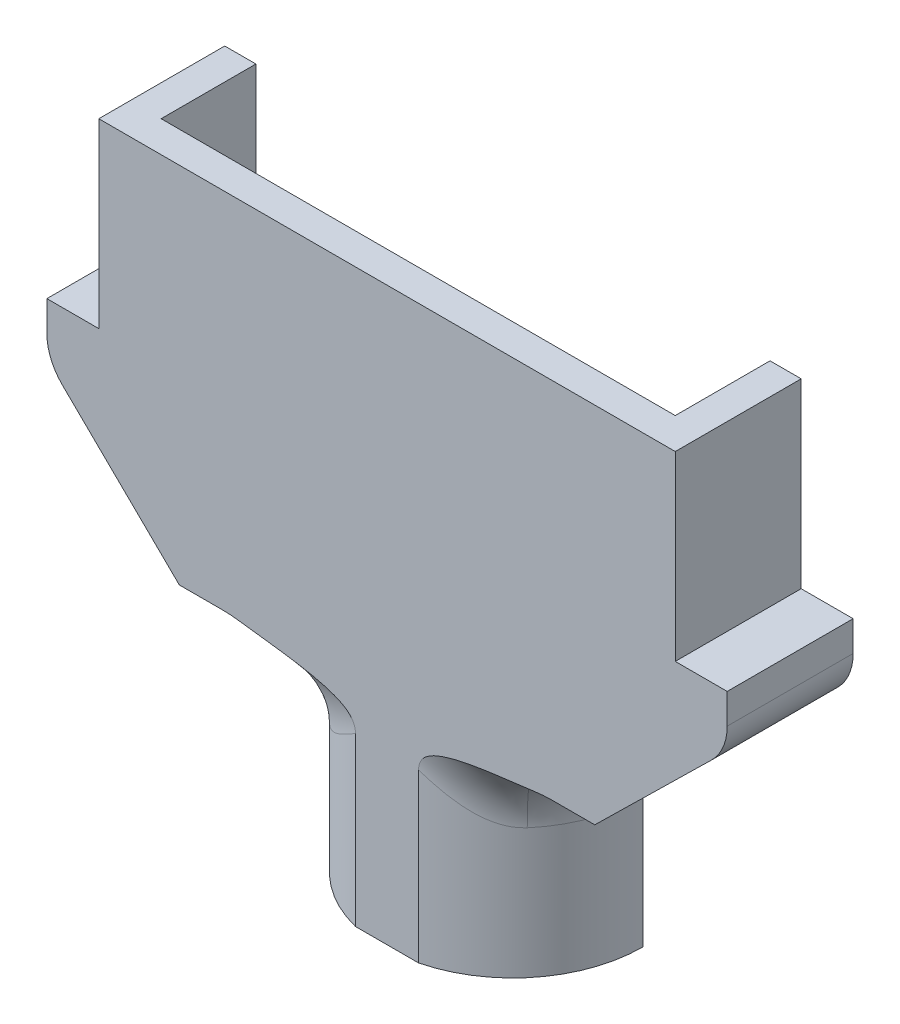
SolidWorks part; units mm, degrees
ref_plane "Alzado" through (0, 0, 0) normal (0, 0, 1) x (1, 0, 0)
ref_plane "Planta" through (0, 0, 0) normal (0, 1, 0) x (1, 0, 0)
ref_plane "Vista lateral" through (0, 0, 0) normal (1, 0, 0) x (0, 0, -1)
sketch "Croquis1" plane through (0, 0, 0) normal (0, 1, 0) x (1, 0, 0)
  line L1 (-9.4, 3.15) -> (9.4, 3.15)
  line L2 (-9.4, 3.15) -> (-9.4, -3.15)
  line L3 (-9.4, -3.15) -> (9.4, -3.15)
  line L4 (9.4, 3.15) -> (9.4, -3.15)
  line L5 (-11.4, 5.15) -> (11.4, 5.15)
  line L6 (-11.4, 5.15) -> (-11.4, -5.15)
  line L7 (-11.4, -5.15) -> (11.4, -5.15)
  line L8 (11.4, 5.15) -> (11.4, -5.15)
  point P4 (0, 3.15)
  point P6 (9.4, 0)
  point P11 (-9.4, 0)
  dimension "D1" = 18.8
  dimension "D2" = 6.3
  dimension "D3" = 2
  dimension "D4" = 2
  dimension "D5" = 2
  dimension "D6" = 2
extrude "Saliente-Extruir1" add sketch "Croquis1" along normal blind 7
sketch "Croquis3" plane through (0, 0, 0) normal (0, 0, 1) x (1, 0, 0)
  line L0 (-11.4, 0) -> (11.4, 0) construction
  line L1 (-14.4, 0) -> (14.4, 0)
  line L2 (-14.4, 0) -> (-14.4, -7)
  line L3 (-14.4, -7) -> (14.4, -7)
  line L4 (14.4, 0) -> (14.4, -7)
  line L5 (-11.4, 7) -> (-11.4, 0) construction
  line L6 (11.4, 7) -> (11.4, 0) construction
  line L8 (-5, -7) -> (5, -7)
  line L9 (-5, -7) -> (-5, -15)
  line L10 (-5, -15) -> (5, -15)
  line L11 (5, -7) -> (5, -15)
  point P14 (0, -15)
  dimension "D1" = 3
  dimension "D2" = 3
  dimension "D3" = 7
  dimension "D4" = 10
  dimension "D5" = 8
extrude "Saliente-Extruir3" add sketch "Croquis3" along normal blind 5.2 contours L4 L1 L2 L3 | L11 L3 L9 L10 region at (0, -3.5, 0) region at (0, -11, 0)
sketch "Croquis4" plane through (0, -15, 0) normal (0, -1, 0) x (1, 0, 0)
  line L1 (-9.3409, 11.3798) -> (8.5543, 11.3798)
  line L2 (-9.3409, 11.3798) -> (-9.3409, -7.874)
  line L3 (-9.3409, -7.874) -> (8.5543, -7.874)
  line L4 (8.5543, 11.3798) -> (8.5543, -7.874)
  circle A0 centre (0, 0) radius 3.4
  circle A1 centre (0, 0) radius 5
  line M5 (-5, 0) -> (5, 0)
  line M6 (5, 0) -> (5, 5.2)
  line M7 (5, 5.2) -> (-5, 5.2)
  line M8 (-5, 5.2) -> (-5, 0)
  dimension "D1" = 6.8
extrude "Cortar-Extruir1" cut sketch "Croquis4" against normal up to surface (8 mm away) contours L4 L1 L2 L3 A1 M8 M7 M6 | A0 M5 | A1 M6 M7 M8 region at (-0.3933, -15, 11.1169) region at (0, -15, 1.443) region at (0, -15, 5.1127) up to face at (9.7, -7, 2.6)
sketch "Croquis5" plane through (0, -7, 0) normal (0, -1, 0) x (1, 0, 0)
  line L1 (-3.4, 0) -> (3.4, 0)
  line L2 (-3.4, 0) -> (3.4, 0)
  arc A1 (3.4, 0) -> (-3.4, 0) centre (0, 0) ccw
  arc A2 (3.4, 0) -> (-3.4, 0) centre (0, 0) ccw
  dimension "D1" = 0
extrude "Cortar-Extruir2" cut sketch "Croquis5" against normal blind 26.4
sketch "Croquis6" plane through (0, 0, -5.15) normal (0, 0, -1) x (-1, 0, 0)
  line L4 (-11.4, 0) -> (11.4, 0)
  line L5 (11.4, 0) -> (11.4, 7)
  line L6 (11.4, 7) -> (-11.4, 7)
  line L7 (-11.4, 7) -> (-11.4, 0)
  line L8 (-11.4, 0) -> (11.4, 0)
  line L9 (11.4, 0) -> (11.4, 7)
  line L10 (11.4, 7) -> (-11.4, 7)
  line L11 (-11.4, 7) -> (-11.4, 0)
  dimension "D1" = 0
extrude "Cortar-Extruir3" cut sketch "Croquis6" against normal up to surface (5.15 mm away) up to face at (8.3, -5.5, 0)
fillet "Redondeo3" radius 3 1 edges at (0, -7, 5)
sketch "Croquis7" plane through (0, 7, 0) normal (0, 1, 0) x (1, 0, 0)
  line L0 (9.4, 0) -> (11.4, 0) construction
  line L1 (9.9, 0) -> (-9.9, 0)
  line L2 (9.9, 0) -> (9.9, -3.65)
  line L3 (9.9, -3.65) -> (-9.9, -3.65)
  line L4 (-9.9, 0) -> (-9.9, -3.65)
  line L7 (-11.4, -5.15) -> (11.4, -5.15) construction
  line L8 (11.1, 0) -> (11.1, -4.85)
  line L9 (11.1, -4.85) -> (-11.1, -4.85)
  line L10 (-11.1, -4.85) -> (-11.1, 0)
  line L11 (-11.4, 0) -> (-9.4, 0) construction
  line L12 (-11.1, 0) -> (-13.1406, 0)
  line L13 (-13.1406, 0) -> (-13.1406, -7.2853)
  line L14 (-13.1406, -7.2853) -> (14.3364, -7.2853)
  line L15 (14.3364, -7.2853) -> (14.0781, 0)
  line L16 (14.0781, 0) -> (11.1, 0)
  line L18 (11.4, -5.15) -> (11.4, 0) construction
  line L19 (-11.4, 0) -> (-11.4, -5.15) construction
  dimension "D1" = 1.2
  dimension "D2" = 1.2
  dimension "D3" = 1.5
  dimension "D4" = 1.2
  dimension "D5" = 1.5
  dimension "D6" = 1.5
extrude "Cortar-Extruir4" cut sketch "Croquis7" against normal up to surface (7 mm away) up to face at (0, 0, 2.5875)
sketch "Croquis8" plane through (0, 0, 0) normal (0, 0, -1) x (-1, 0, 0)
  line L0 (-9.9, 0) -> (-3.4, -7.5)
  line L1 (-3.4, 0) -> (-3.4, -15) construction
  line L2 (-3.4, -7.5) -> (3.4, -7.5)
  line L3 (3.4, 0) -> (3.4, -15) construction
  line L4 (3.4, -7.5) -> (9.9, 0)
  line L5 (9.9, 0) -> (-9.9, 0)
extrude "Cortar-Extruir5" cut sketch "Croquis8" against normal up to surface (3.65 mm away) up to face at (0, 3.5, 3.65)
sketch "Croquis9" plane through (0, 0, 5.2) normal (0, 0, 1) x (1, 0, 0)
  line L0 (-13.1, -2) -> (-8, -7)
  line L2 (-8, -7) -> (-16.9683, -7)
  line L3 (-16.9683, -7) -> (-16.9683, -2)
  line L5 (-11.1, 0) -> (-11.1, 7) construction
  line L6 (-14.4, 0) -> (14.4, 0) construction
  line L7 (-13.1, -2) -> (-13.1, 0)
  line L8 (-13.1, 0) -> (-17.2008, 0)
  line L9 (-17.2008, 0) -> (-16.9683, -2)
  line L10 (0, 0) -> (0, -3.6062) construction
  line L11 (17.2008, 0) -> (16.9683, -2)
  line L12 (13.1, 0) -> (17.2008, 0)
  line L13 (13.1, -2) -> (13.1, 0)
  line L14 (16.9683, -7) -> (16.9683, -2)
  line L15 (8, -7) -> (16.9683, -7)
  line L16 (13.1, -2) -> (8, -7)
  dimension "D1" = 2
extrude "Cortar-Extruir6" cut sketch "Croquis9" against normal blind 10
fillet "Redondeo4" radius 2 2 edges at (-13.1, -2, 2.6) (13.1, -2, 2.6)
sketch "Croquis10" plane through (0, 0, 0) normal (0, 1, 0) x (1, 0, 0)
  line L1 (-17.4383, -12.8397) -> (20.5886, -12.8397)
  line L2 (-17.4383, -12.8397) -> (-17.4383, -4.85)
  line L3 (-17.4383, -4.85) -> (20.5886, -4.85)
  line L4 (20.5886, -12.8397) -> (20.5886, -4.85)
  line L6 (-11.1, -4.85) -> (11.1, -4.85) construction
extrude "Cortar-Extruir7" cut sketch "Croquis10" against normal blind 21
